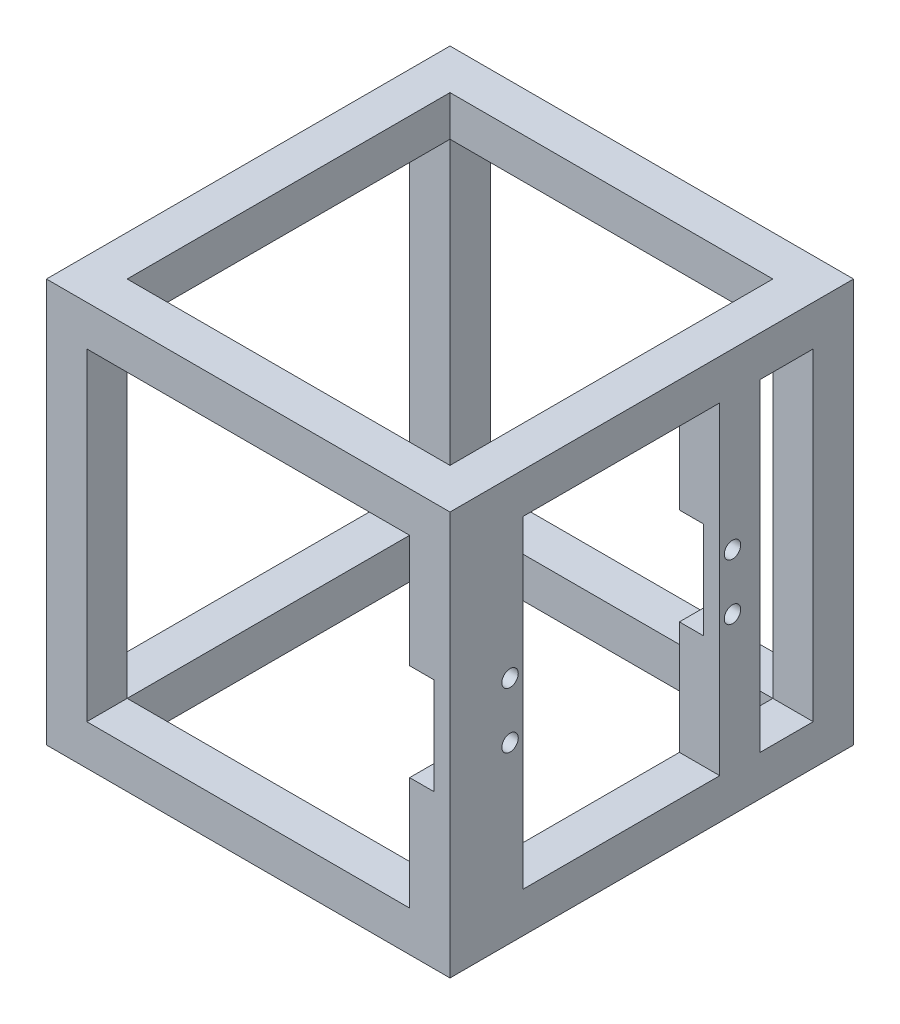
SolidWorks part; units mm, degrees
ref_plane "Front Plane" through (0, 0, 0) normal (0, 0, 1) x (1, 0, 0)
ref_plane "Top Plane" through (0, 0, 0) normal (0, 1, 0) x (1, 0, 0)
ref_plane "Right Plane" through (0, 0, 0) normal (1, 0, 0) x (0, 0, -1)
sketch "Sketch1" plane through (0, 0, 0) normal (0, 0, 1) x (1, 0, 0)
  line L1 (0, 0) -> (-50, 0)
  line L2 (0, 0) -> (0, 50)
  line L3 (0, 50) -> (-50, 50)
  line L4 (-50, 0) -> (-50, 50)
  line L5 (-45, 45) -> (-5, 45)
  line L6 (-45, 45) -> (-45, 5)
  line L7 (-45, 5) -> (-5, 5)
  line L8 (-5, 45) -> (-5, 5)
  dimension "D1" = 50
  dimension "D2" = 50
  dimension "D3" = 40
  dimension "D4" = 40
  dimension "D5" = 5
  dimension "D6" = 5
extrude "Extrude1" add sketch "Sketch1" along normal blind 50
sketch "Sketch2" plane through (0, 0, 0) normal (0, -1, 0) x (1, 0, 0)
  line L0 (-50, 50) -> (0, 50) construction
  line L1 (-5, 45) -> (-45, 45)
  line L2 (-5, 45) -> (-5, 5)
  line L3 (-5, 5) -> (-45, 5)
  line L4 (-45, 45) -> (-45, 5)
  line L5 (0, 50) -> (0, 0) construction
  dimension "D1" = 5
  dimension "D2" = 5
  dimension "D3" = 40
  dimension "D4" = 40
extrude "Cut-Extrude1" cut sketch "Sketch2" against normal blind 50
sketch "Sketch3" plane through (-50, 0, 0) normal (-1, 0, 0) x (0, 0, 1)
  line L0 (50, 50) -> (0, 50) construction
  line L1 (5, 45) -> (45, 45)
  line L2 (5, 45) -> (5, 5)
  line L3 (5, 5) -> (45, 5)
  line L4 (45, 45) -> (45, 5)
  line L5 (0, 50) -> (0, 0) construction
  dimension "D1" = 5
  dimension "D2" = 5
  dimension "D3" = 40
  dimension "D4" = 40
extrude "Cut-Extrude2" cut sketch "Sketch3" against normal blind 10
sketch "Sketch4" plane through (0, 0, 0) normal (1, 0, 0) x (0, 0, -1)
  line L0 (-40.7795, 31) -> (-40.7795, 24.9871) construction
  line L1 (-40.9795, 5) -> (-16.5795, 5)
  line L2 (-40.9795, 5) -> (-40.9795, 45)
  line L3 (-40.9795, 45) -> (-16.5795, 45)
  line L4 (-16.5795, 5) -> (-16.5795, 45)
  line L5 (-16.7795, 19) -> (-16.7795, 31) construction
  line L6 (-50, 50) -> (0, 50) construction
  line L7 (0, 0) -> (0, 50) construction
  line L8 (-5, 45) -> (-11.5795, 45)
  line L9 (-5, 45) -> (-5, 5)
  line L10 (-5, 5) -> (-11.5795, 5)
  line L11 (-11.5795, 45) -> (-11.5795, 5)
  dimension "D1" = 0.2
  dimension "D2" = 0.2
  dimension "D3" = 5
  dimension "D4" = 40
  dimension "D5" = 5
  dimension "D6" = 5
  dimension "D7" = 40
  dimension "D8" = 5
extrude "Cut-Extrude3" cut sketch "Sketch4" against normal blind 10
sketch "Sketch5" plane through (0, 0, 0) normal (1, 0, 0) x (0, 0, -1)
  line L0 (-28.7795, 47.056) -> (-28.7795, 3.9656) construction
  line L2 (-16.5795, 5) -> (-16.5795, 45) construction
  line L3 (-40.9795, 45) -> (-40.9795, 5) construction
  circle A0 centre (-42.5575, 28.46) radius 1.016
  circle A1 centre (-42.5575, 21.5362) radius 1.016
  circle A2 centre (-15.0015, 21.5362) radius 1.016
  circle A3 centre (-15.0015, 28.46) radius 1.016
  circle A5 centre (-42.5575, 28.46) radius 1.016 construction
  circle A6 centre (-42.5575, 21.5362) radius 1.016 construction
extrude "Cut-Extrude4" cut sketch "Sketch5" against normal blind 10
sketch "Sketch6" plane through (0, 0, 50) normal (0, 0, 1) x (1, 0, 0)
  line L0 (-5, 5) -> (-5, 45) construction
  line L1 (-5, 31) -> (-2, 31)
  line L2 (-5, 31) -> (-5, 19)
  line L3 (-5, 19) -> (-2, 19)
  line L4 (-2, 31) -> (-2, 19)
  line L5 (-0.2, 19) -> (-17.2, 19) construction
  line L6 (-0.2, 31) -> (-17.2, 31) construction
  line L7 (0, 0) -> (0, 50) construction
  dimension "D1" = 2
extrude "Cut-Extrude5" cut sketch "Sketch6" against normal blind 40
